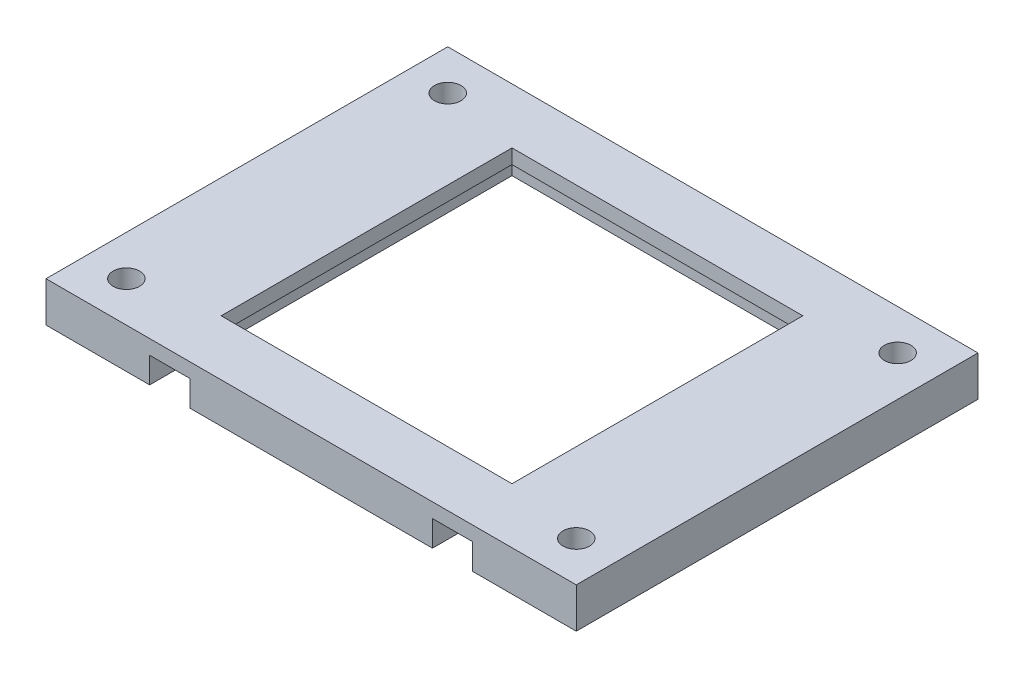
SolidWorks part; units mm, degrees
ref_plane "Front Plane" through (0, 0, 0) normal (0, 0, 1) x (1, 0, 0)
ref_plane "Top Plane" through (0, 0, 0) normal (0, 1, 0) x (1, 0, 0)
ref_plane "Right Plane" through (0, 0, 0) normal (1, 0, 0) x (0, 0, -1)
sketch "Sketch1" plane through (0, 0, 0) normal (0, 1, 0) x (1, 0, 0)
  line L1 (-20.1, -20.1) -> (20.1, -20.1)
  line L2 (-20.1, -20.1) -> (-20.1, 20.1)
  line L3 (-20.1, 20.1) -> (20.1, 20.1)
  line L4 (20.1, -20.1) -> (20.1, 20.1)
  line L5 (-20.1, -20.1) -> (20.1, 20.1) construction
  line L6 (-20.1, 20.1) -> (20.1, -20.1) construction
  line L7 (-33, -25) -> (33, -25)
  line L8 (-33, -25) -> (-33, 25)
  line L9 (-33, 25) -> (33, 25)
  line L10 (33, -25) -> (33, 25)
  line L11 (-33, -25) -> (33, 25) construction
  line L12 (-33, 25) -> (33, -25) construction
  circle A0 centre (-28, 20) radius 1.65
  circle A1 centre (28, 20) radius 1.65
  circle A2 centre (-28, -20) radius 1.65
  circle A3 centre (28, -20) radius 1.65
  point P0 (0, 0)
  point P15 (0, 0)
  dimension "D3" = 20
  dimension "D4" = 20
  dimension "D5" = 20
  dimension "D6" = 20
  dimension "D7" = 28
  dimension "D10" = 28
  dimension "D11" = 3.3
  dimension "D1" = 40.2
  dimension "D2" = 40.2
  dimension "D8" = 28
  dimension "D9" = 28
  dimension "D12" = 66
  dimension "D13" = 50
extrude "Boss-Extrude1" add sketch "Sketch1" along normal blind 5
sketch "Sketch2" plane through (0, 5, 0) normal (0, 1, 0) x (1, 0, 0)
  line L8 (-18.1, -18.1) -> (18.1, -18.1)
  line L9 (18.1, -18.1) -> (18.1, 18.1)
  line L10 (-18.1, 18.1) -> (-18.1, -18.1)
  line L11 (18.1, 18.1) -> (-18.1, 18.1)
  line L12 (-18.1, -18.1) -> (18.1, -18.1)
  line L13 (18.1, -18.1) -> (18.1, 18.1)
  line L14 (-18.1, 18.1) -> (-18.1, -18.1)
  line L15 (18.1, 18.1) -> (-18.1, 18.1)
  line L20 (-20.1, -20.1) -> (20.1, -20.1)
  line L21 (20.1, -20.1) -> (20.1, 20.1)
  line L22 (-20.1, 20.1) -> (-20.1, -20.1)
  line L23 (20.1, 20.1) -> (-20.1, 20.1)
  line L24 (-20.1, -20.1) -> (20.1, -20.1)
  line L25 (20.1, -20.1) -> (20.1, 20.1)
  line L26 (-20.1, 20.1) -> (-20.1, -20.1)
  line L27 (20.1, 20.1) -> (-20.1, 20.1)
  dimension "D1" = 2
  dimension "D2" = 0
extrude "Boss-Extrude2" add sketch "Sketch2" against normal blind 1.8
sketch "Sketch3" plane through (0, 0, 25) normal (0, 0, 1) x (1, 0, 0)
  line L0 (-33, 0) -> (33, 0) construction
  line L1 (-20.1, 0) -> (-15.1, 0)
  line L2 (-20.1, 0) -> (-20.1, 3.2)
  line L3 (-20.1, 3.2) -> (-15.1, 3.2)
  line L4 (-15.1, 0) -> (-15.1, 3.2)
  line L6 (20.1, 0) -> (15.1, 0)
  line L7 (20.1, 0) -> (20.1, 3.2)
  line L8 (20.1, 3.2) -> (15.1, 3.2)
  line L9 (15.1, 0) -> (15.1, 3.2)
  dimension "D1" = 5
  dimension "D2" = 5
  dimension "D3" = 0
  dimension "D4" = 0
  dimension "D5" = 3.2
  dimension "D6" = 3.2
extrude "Cut-Extrude1" cut sketch "Sketch3" against normal up to next
